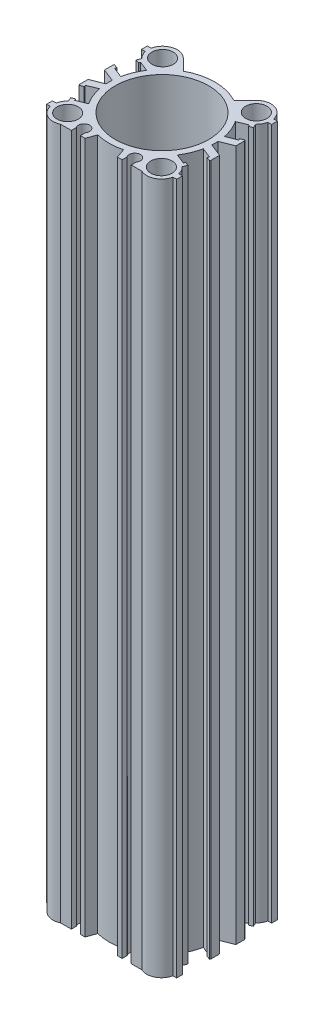
SolidWorks part; units mm, degrees
material "1.0715 (11SMn30)"
ref_plane "Alzado" through (0, 0, 0) normal (0, 0, 1) x (1, 0, 0)
ref_plane "Planta" through (0, 0, 0) normal (0, 1, 0) x (1, 0, 0)
ref_plane "Vista lateral" through (0, 0, 0) normal (1, 0, 0) x (0, 0, -1)
sketch "Croquis1" plane through (0, 0, 0) normal (0, 1, 0) x (1, 0, 0)
  line L0 (-23.9675, 0) -> (21.5896, 0) construction
  line L5 (0, 21.2788) -> (0, -19.2653) construction
  line L6 (15.5747, 0) -> (18.1195, 1.0523) construction
  line L7 (22.5195, 2.8033) -> (22.5195, 5.7033)
  line L8 (18.1195, 1.0523) -> (22.5195, 2.8033)
  line L9 (22.5195, 5.7033) -> (22.3603, 6.1033)
  line L10 (22.3603, 6.1033) -> (21.0603, 5.586)
  line L11 (21.0603, 5.586) -> (21.2821, 5.0285)
  line L12 (21.2821, 5.0285) -> (17.7821, 3.6357)
  line L13 (15.1971, 9.9232) -> (18.6349, 11.2912)
  line L14 (18.6349, 11.2912) -> (18.8568, 10.7338)
  line L15 (18.8568, 10.7338) -> (20.0646, 11.2144)
  line L16 (20.0646, 11.2144) -> (19.51, 12.6081)
  line L17 (8.6563, 15.9528) -> (12.6161, 19.9126)
  line L18 (12.6161, 19.9126) -> (19.51, 12.6081) construction
  line L19 (20.9845, 17.2604) -> (22.2845, 17.2604)
  line L20 (22.2845, 17.2604) -> (22.2845, 15.2604)
  line L21 (22.2845, 15.2604) -> (20.9845, 15.2604)
  line L22 (-12.6161, 19.9126) -> (-19.51, 12.6081) construction
  line L23 (-15.5747, 0) -> (-18.1195, 1.0523) construction
  line L24 (-22.2845, 15.2604) -> (-20.9845, 15.2604)
  line L25 (-22.2845, 17.2604) -> (-22.2845, 15.2604)
  line L26 (-20.9845, 17.2604) -> (-22.2845, 17.2604)
  line L27 (-8.6563, 15.9528) -> (-12.6161, 19.9126)
  line L28 (-20.0646, 11.2144) -> (-19.51, 12.6081)
  line L29 (-18.8568, 10.7338) -> (-20.0646, 11.2144)
  line L30 (-18.6349, 11.2912) -> (-18.8568, 10.7338)
  line L31 (-15.1971, 9.9232) -> (-18.6349, 11.2912)
  line L32 (-21.2821, 5.0285) -> (-17.7821, 3.6357)
  line L33 (-21.0603, 5.586) -> (-21.2821, 5.0285)
  line L34 (-22.3603, 6.1033) -> (-21.0603, 5.586)
  line L35 (-22.5195, 5.7033) -> (-22.3603, 6.1033)
  line L36 (-18.1195, 1.0523) -> (-22.5195, 2.8033)
  line L37 (-22.5195, 2.8033) -> (-22.5195, 5.7033)
  line L38 (-15.5747, 0) -> (-18.1195, -1.0523) construction
  line L39 (-12.6161, -19.9126) -> (-19.51, -12.6081) construction
  line L40 (12.6161, -19.9126) -> (19.51, -12.6081) construction
  line L41 (15.5747, 0) -> (18.1195, -1.0523) construction
  line L42 (-22.5195, -2.8033) -> (-22.5195, -5.7033)
  line L43 (-18.1195, -1.0523) -> (-22.5195, -2.8033)
  line L44 (-22.5195, -5.7033) -> (-22.3603, -6.1033)
  line L45 (-22.3603, -6.1033) -> (-21.0603, -5.586)
  line L46 (-21.0603, -5.586) -> (-21.2821, -5.0285)
  line L47 (-21.2821, -5.0285) -> (-17.7821, -3.6357)
  line L48 (-15.1971, -9.9232) -> (-18.6349, -11.2912)
  line L49 (-18.6349, -11.2912) -> (-18.8568, -10.7338)
  line L50 (-18.8568, -10.7338) -> (-20.0646, -11.2144)
  line L51 (-20.0646, -11.2144) -> (-19.51, -12.6081)
  line L53 (-20.9845, -17.2604) -> (-22.2845, -17.2604)
  line L54 (-22.2845, -17.2604) -> (-22.2845, -15.2604)
  line L55 (-22.2845, -15.2604) -> (-20.9845, -15.2604)
  line L56 (22.2845, -15.2604) -> (20.9845, -15.2604)
  line L57 (22.2845, -17.2604) -> (22.2845, -15.2604)
  line L58 (20.9845, -17.2604) -> (22.2845, -17.2604)
  line L60 (20.0646, -11.2144) -> (19.51, -12.6081)
  line L61 (18.8568, -10.7338) -> (20.0646, -11.2144)
  line L62 (18.6349, -11.2912) -> (18.8568, -10.7338)
  line L63 (15.1971, -9.9232) -> (18.6349, -11.2912)
  line L64 (21.2821, -5.0285) -> (17.7821, -3.6357)
  line L65 (21.0603, -5.586) -> (21.2821, -5.0285)
  line L66 (22.3603, -6.1033) -> (21.0603, -5.586)
  line L67 (22.5195, -5.7033) -> (22.3603, -6.1033)
  line L68 (18.1195, -1.0523) -> (22.5195, -2.8033)
  line L69 (22.5195, -2.8033) -> (22.5195, -5.7033)
  line L70 (-13.9363, -20.8098) -> (-10.2554, -20.8098)
  line L71 (-10.2554, -20.8098) -> (-10.2554, -19.1098)
  line L72 (-10.2554, -19.1098) -> (-7.1554, -19.1098) construction
  line L73 (-7.1554, -19.1098) -> (-7.1554, -20.8098)
  line L74 (-7.1554, -20.8098) -> (-5.5554, -20.8098)
  line L75 (-5.5554, -20.8098) -> (-4.4143, -17.605)
  line L76 (10.2554, -20.8098) -> (10.2554, -19.1098)
  line L77 (13.9363, -20.8098) -> (10.2554, -20.8098)
  line L78 (7.1554, -19.1098) -> (7.1554, -20.8098)
  line L79 (7.1554, -20.8098) -> (5.5554, -20.8098)
  line L80 (5.5554, -20.8098) -> (4.4143, -17.605)
  circle A0 centre (0, 0) radius 16
  arc A1 (-4.4143, -17.605) -> (4.4143, -17.605) centre (0, 0) ccw construction
  arc A2 (17.7821, 3.6357) -> (15.1971, 9.9232) centre (0, 0) ccw
  arc A3 (18.1195, -1.0523) -> (18.1195, 1.0523) centre (0, 0) ccw
  arc A4 (15.1971, 9.9232) -> (8.6563, 15.9528) centre (0, 0) ccw construction
  circle A5 centre (16.063, 16.2604) radius 5.022 construction
  circle A6 centre (16.063, 16.2604) radius 3.65
  arc A7 (12.6161, 19.9126) -> (20.9845, 17.2604) centre (16.063, 16.2604) cw
  arc A8 (20.9845, 15.2604) -> (19.51, 12.6081) centre (16.063, 16.2604) cw
  arc A9 (8.6563, 15.9528) -> (-8.6563, 15.9528) centre (0, 0) ccw
  circle A10 centre (-16.063, 16.2604) radius 5.022 construction
  arc A11 (-20.9845, 15.2604) -> (-19.51, 12.6081) centre (-16.063, 16.2604) ccw
  arc A12 (-12.6161, 19.9126) -> (-20.9845, 17.2604) centre (-16.063, 16.2604) ccw
  circle A13 centre (-16.063, 16.2604) radius 3.65
  arc A14 (-15.1971, 9.9232) -> (-8.6563, 15.9528) centre (0, 0) cw construction
  arc A15 (-18.1195, -1.0523) -> (-18.1195, 1.0523) centre (0, 0) cw
  arc A16 (-17.7821, 3.6357) -> (-15.1971, 9.9232) centre (0, 0) cw
  arc A17 (-11.5987, -13.9604) -> (-13.9363, -20.8098) centre (-16.063, -16.2604) ccw construction
  arc A18 (11.5987, -13.9604) -> (13.9363, -20.8098) centre (16.063, -16.2604) cw construction
  arc A19 (-17.7821, -3.6357) -> (-15.1971, -9.9232) centre (0, 0) ccw
  arc A20 (-7.1554, -19.1098) -> (-10.2554, -19.1098) centre (-8.7054, -18.0098) ccw
  circle A21 centre (-16.063, -16.2604) radius 3.65
  arc A22 (-13.9363, -20.8098) -> (-20.9845, -17.2604) centre (-16.063, -16.2604) cw
  arc A23 (-20.9845, -15.2604) -> (-19.51, -12.6081) centre (-16.063, -16.2604) cw
  arc A25 (20.9845, -15.2604) -> (19.51, -12.6081) centre (16.063, -16.2604) ccw
  arc A26 (13.9363, -20.8098) -> (20.9845, -17.2604) centre (16.063, -16.2604) ccw
  circle A27 centre (16.063, -16.2604) radius 3.65
  arc A28 (15.1971, -9.9232) -> (8.6563, -15.9528) centre (0, 0) cw construction
  arc A29 (17.7821, -3.6357) -> (15.1971, -9.9232) centre (0, 0) cw
  arc A30 (7.1554, -19.1098) -> (10.2554, -19.1098) centre (8.7054, -18.0098) cw
  arc A31 (8.6563, -15.9528) -> (-8.6563, -15.9528) centre (0, 0) ccw construction
  arc A32 (4.4143, -17.605) -> (-4.4143, -17.605) centre (0, 0) cw
  point P28 (16.063, 16.2604)
  point P62 (-16.063, 16.2604)
  point P103 (-16.063, -16.2604)
  point P104 (16.063, -16.2604)
  dimension "D1" = 32
  dimension "D2" = 36.3
  dimension "D3" = 21.7
  dimension "D20" = 7.3
  dimension "D31" = 3.8013
  dimension "D4" = 4.4
  dimension "D5" = 2.9
  dimension "D6" = 21.7
  dimension "D7" = 0.4
  dimension "D8" = 90
  dimension "D9" = 1.3
  dimension "D10" = 90
  dimension "D11" = 0.6
  dimension "D12" = 3.5
  dimension "D13" = 0
  dimension "D14" = 3.7
  dimension "D15" = 0.6
  dimension "D16" = 1.3
  dimension "D17" = 1.5
  dimension "D18" = 5.6
  dimension "D19" = 23.3
  dimension "D21" = 1.3
  dimension "D22" = 2
  dimension "D23" = 1.3
  dimension "D25" = 1.6
  dimension "D26" = 3.1
  dimension "D27" = 3.6809
  dimension "D30" = 1.7
extrude "Saliente-Extruir1" add sketch "Croquis1" along normal blind 118.5 and the other way blind 118.5
sketch "Croquis5" plane through (0, 0, 0) normal (0, 1, 0) x (1, 0, 0)
  circle A0 centre (16.063, -16.2604) radius 3.65
  circle A1 centre (-16.063, -16.2604) radius 3.65
ref_plane "Plano1" through (0, 0, 23.25) normal (0, 0, 1) x (1, 0, 0)
ref_plane "Plano2" through (23.25, 0, 0) normal (1, 0, 0) x (0, 0, -1)
